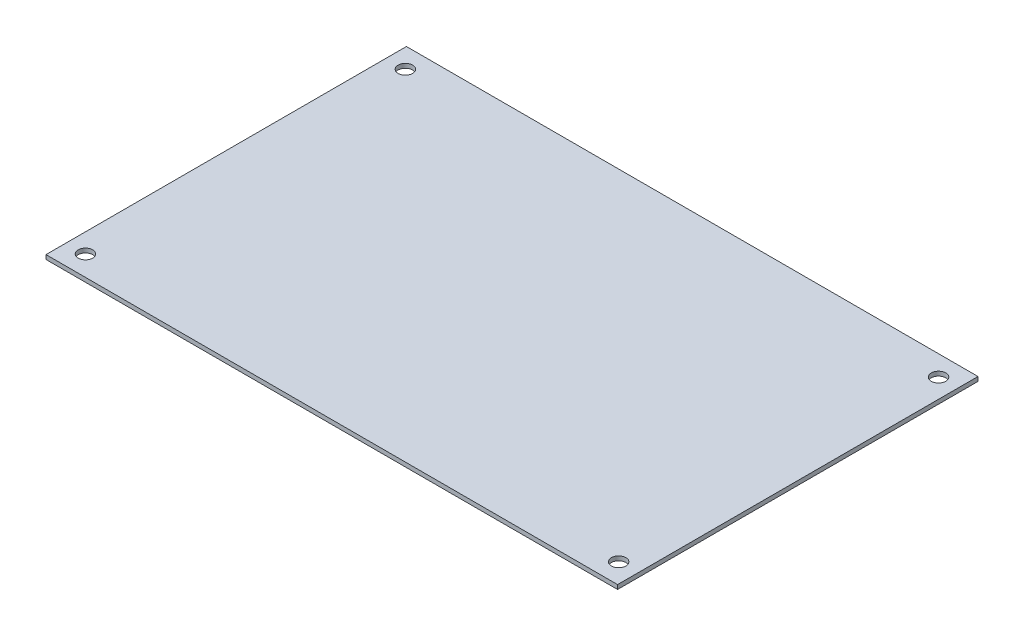
SolidWorks part; units mm, degrees
material "Thornel Mat VMA"
ref_plane "Front Plane" through (0, 0, 0) normal (0, 0, 1) x (1, 0, 0)
ref_plane "Top Plane" through (0, 0, 0) normal (0, 1, 0) x (1, 0, 0)
ref_plane "Right Plane" through (0, 0, 0) normal (1, 0, 0) x (0, 0, -1)
sketch "Sketch1" plane through (0, 0, 0) normal (0, 1, 0) x (1, 0, 0)
  line L1 (0, 0) -> (134, 0)
  line L2 (0, 0) -> (0, 84.5)
  line L3 (0, 84.5) -> (134, 84.5)
  line L4 (134, 0) -> (134, 84.5)
  dimension "D1" = 134
  dimension "D2" = 84.5
extrude "Boss-Extrude1" add sketch "Sketch1" along normal blind 1
sketch "Sketch2" plane through (0, 1, 0) normal (0, 1, 0) x (1, 0, 0)
  line L0 (67, 42.25) -> (67, 84.5) construction
  line L2 (134, 84.5) -> (0, 84.5) construction
  line L3 (129.5, 79.75) -> (4.5, 79.75) construction
  line L4 (129.5, 79.75) -> (129.5, 4.75) construction
  line L5 (129.5, 4.75) -> (4.5, 4.75) construction
  line L6 (4.5, 79.75) -> (4.5, 4.75) construction
  line L7 (129.5, 79.75) -> (4.5, 4.75) construction
  line L8 (129.5, 4.75) -> (4.5, 79.75) construction
  line L11 (0, 0) -> (134, 0) construction
  line L13 (134, 0) -> (134, 84.5) construction
  line L14 (67, 42.25) -> (134, 42.25) construction
  line L15 (67, 42.25) -> (0, 42.25) construction
  line L16 (0, 84.5) -> (0, 0) construction
  line L17 (67, 42.25) -> (67, 0) construction
  circle A0 centre (4.5, 4.75) radius 1.6
  circle A1 centre (4.5, 79.75) radius 1.6
  circle A2 centre (129.5, 79.75) radius 1.6
  circle A3 centre (129.5, 4.75) radius 1.6
  point P8 (67, 42.25)
  dimension "D1" = 3.2
  dimension "D2" = 125
  dimension "D3" = 75
hole_wizard "M3 Clearance Hole1" positions "Sketch4" profile "Sketch3" hole size "M3" standard "ANSI Metric"
sketch "Sketch4" plane through (0, 1, 0) normal (0, 1, 0) x (1, 0, 0)
  point P0 (4.5, 79.75)
  point P3 (129.5, 79.75)
  point P6 (129.5, 4.75)
  point P9 (4.5, 4.75)
sketch "Sketch3" plane through (4.5, 1, -79.75) normal (1, 0, 0) x (0, 0, 1)
  line L0 (0, 0) -> (0, 6.0215)
  line L1 (0, 6.0215) -> (1.7, 5)
  line L2 (1.7, 5) -> (1.7, 0)
  line L5 (1.7, 0) -> (0, 0)
  line L10 (0, 6.0215) -> (-1.7, 5) construction
  line L11 (0, -6.35) -> (0, 107.95) construction
  dimension "Hole Dia." = 3.4
  dimension "Hole Depth" = 5
  dimension "Drill Angle" = 118
